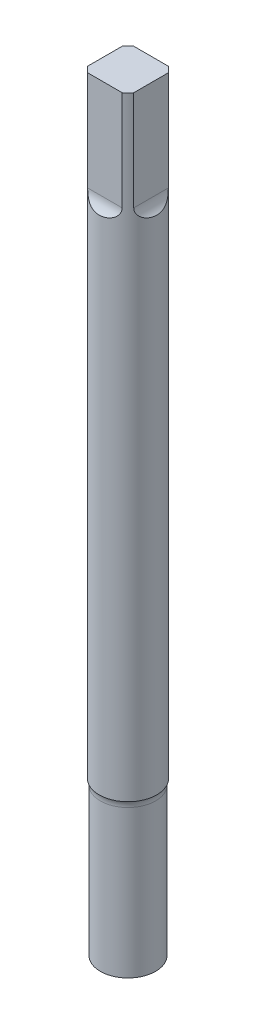
SolidWorks part; units mm, degrees
ref_plane "Front Plane" through (0, 0, 0) normal (0, 0, 1) x (1, 0, 0)
ref_plane "Top Plane" through (0, 0, 0) normal (0, 1, 0) x (1, 0, 0)
ref_plane "Right Plane" through (0, 0, 0) normal (1, 0, 0) x (0, 0, -1)
sketch "Sketch1" plane through (0, 0, 0) normal (0, 1, 0) x (1, 0, 0)
  circle A0 centre (0, 0) radius 4.7625
  dimension "D1" = 9.525
extrude "Boss-Extrude1" add sketch "Sketch1" against normal blind 101.6
sketch "Sketch2" plane through (0, 0, 0) normal (0, 1, 0) x (1, 0, 0)
  line L1 (-5.2709, 3.81) -> (-5.2709, 5.9454)
  line L2 (-5.2709, 5.9454) -> (6.0444, 5.9454)
  line L3 (6.0444, 5.9454) -> (6.0444, 3.81)
  line L5 (-5.2709, 3.81) -> (6.0444, 3.81)
  line L10 (5.2709, -3.81) -> (-6.0444, -3.81)
  line L11 (-6.0444, -5.9454) -> (-6.0444, -3.81)
  line L12 (5.2709, -5.9454) -> (-6.0444, -5.9454)
  line L13 (5.2709, -3.81) -> (5.2709, -5.9454)
  line L18 (-5.9454, -5.2709) -> (-5.9454, 6.0444) [skipped]
  line L19 (-3.81, -5.2709) -> (-3.81, 6.0444) [skipped]
  line L20 (-3.81, -5.2709) -> (-5.9454, -5.2709) [skipped]
  line L21 (-5.9454, 6.0444) -> (-3.81, 6.0444) [skipped]
  line L22 (3.81, 5.2709) -> (3.81, -6.0444) [skipped]
  line L23 (3.81, 5.2709) -> (5.9454, 5.2709) [skipped]
  line L24 (5.9454, 5.2709) -> (5.9454, -6.0444) [skipped]
  line L25 (5.9454, -6.0444) -> (3.81, -6.0444) [skipped]
  line L26 (0, 0) -> (0, -3.81) construction
  line L27 (0, 0) -> (0, 3.81) construction
  circle A1 centre (0, 0) radius 4.7625 construction
  point P22 (0, 0)
  dimension "D1" = 3.81
  dimension "D3" = 5.2709
  dimension "D4" = 5.9454
  dimension "D5" = 6.0444
  dimension "D2" = 4
extrude "Cut-Extrude1" cut sketch "Sketch2" against normal blind 19.05
sketch "Sketch3" plane through (0, 0, 0) normal (0, 1, 0) x (1, 0, 0)
  line L1 (3.81, 3.81) -> (6.251, 3.81)
  line L2 (6.251, 3.81) -> (6.251, -4.2062)
  line L3 (6.251, -4.2062) -> (3.81, -4.2062)
  line L5 (3.81, 3.81) -> (3.81, -4.2062)
  line L10 (-6.251, -3.81) -> (-6.251, 4.2062)
  line L11 (-6.251, 4.2062) -> (-3.81, 4.2062)
  line L12 (-3.81, -3.81) -> (-3.81, 4.2062)
  line L13 (-3.81, -3.81) -> (-6.251, -3.81)
  line L18 (4.2062, 6.251) -> (4.2062, 3.81) [skipped]
  line L19 (-3.81, 6.251) -> (4.2062, 6.251) [skipped]
  line L20 (-3.81, 3.81) -> (4.2062, 3.81) [skipped]
  line L21 (-3.81, 3.81) -> (-3.81, 6.251) [skipped]
  line L22 (3.81, -6.251) -> (-4.2062, -6.251) [skipped]
  line L23 (3.81, -3.81) -> (3.81, -6.251) [skipped]
  line L24 (-4.2062, -6.251) -> (-4.2062, -3.81) [skipped]
  line L25 (3.81, -3.81) -> (-4.2062, -3.81) [skipped]
  line L26 (-2.8575, 3.81) -> (2.8575, 3.81) construction
  line L27 (0, 0) -> (-3.81, 0) construction
  line L28 (0, 0) -> (3.81, 0) construction
  point P22 (0, 0)
  dimension "D1" = 1.3487
  dimension "D3" = 3.3935
  dimension "D2" = 4
extrude "Cut-Extrude2" cut sketch "Sketch3" against normal blind 19.05
fillet "Fillet1" radius 2.54 4 edges at (0, -19.05, -3.81) (3.81, -19.05, 0) (-3.81, -19.05, 0) (0, -19.05, 3.81)
sketch "Sketch4" plane through (0, -101.6, 0) normal (0, -1, 0) x (1, 0, 0)
  circle A0 centre (0, 0) radius 4.572
  dimension "D1" = 9.144
extrude "Boss-Extrude2" add sketch "Sketch4" along normal blind 25.4
fillet "Fillet2" radius 2.54 1 edges at (0, -101.6, -4.572)
